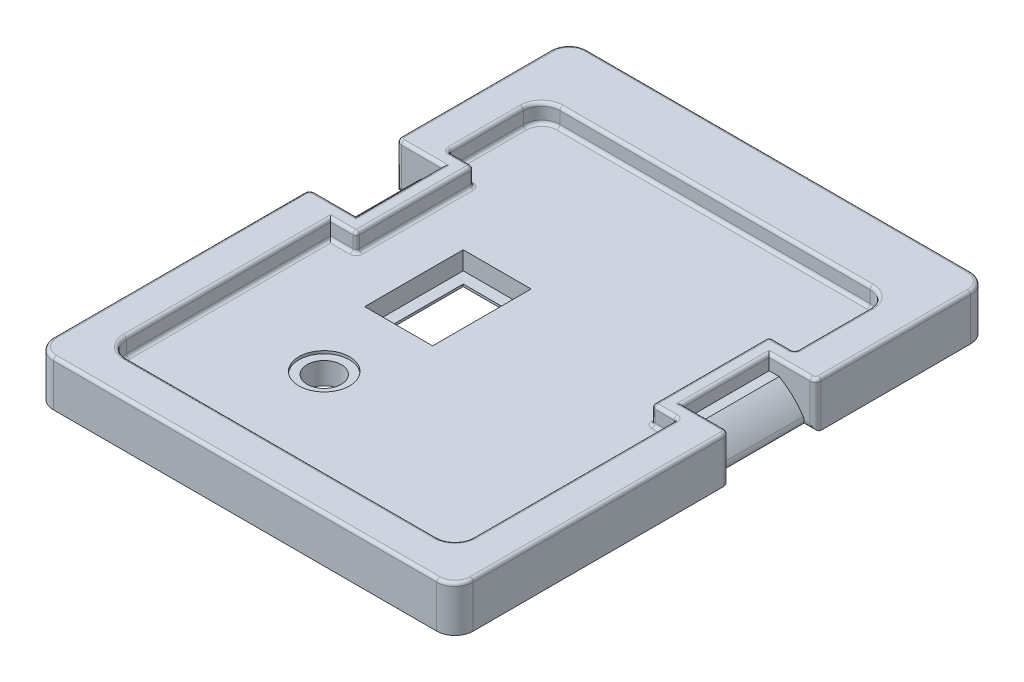
SolidWorks part; units mm, degrees
ref_plane "Front Plane" through (0, 0, 0) normal (0, 0, 1) x (1, 0, 0)
ref_plane "Top Plane" through (0, 0, 0) normal (0, 1, 0) x (1, 0, 0)
ref_plane "Right Plane" through (0, 0, 0) normal (1, 0, 0) x (0, 0, -1)
sketch "Sketch1" plane through (0, 0, 0) normal (0, 1, 0) x (1, 0, 0)
  line L1 (2, 0) -> (44, 0)
  line L2 (0, 2) -> (0, 56.5)
  line L3 (2, 58.5) -> (44, 58.5)
  line L4 (46, 2) -> (46, 56.5)
  arc A0 (0, 2) -> (2, 0) centre (2, 2) ccw
  arc A1 (44, 0) -> (46, 2) centre (44, 2) ccw
  arc A2 (46, 56.5) -> (44, 58.5) centre (44, 56.5) ccw
  arc A3 (2, 58.5) -> (0, 56.5) centre (2, 56.5) ccw
  point P7 (0, 0)
  point P10 (46, 0)
  point P13 (46, 58.5)
  dimension "D3" = 2
  dimension "D1" = 46
  dimension "D2" = 58.5
extrude "Boss-Extrude1" add sketch "Sketch1" along normal blind 5
sketch "Sketch2" plane through (0, 5, 0) normal (0, 1, 0) x (1, 0, 0)
  line L0 (4, 49.5) -> (4, 6)
  line L1 (0, 55.5) -> (46, 55.5)
  line L2 (0, 55.5) -> (0, 0)
  line L3 (0, 0) -> (46, 0)
  line L4 (46, 55.5) -> (46, 0)
  line L5 (6, 4) -> (40, 4)
  line L6 (42, 49.5) -> (42, 6)
  line L7 (6, 51.5) -> (40, 51.5)
  line L8 (42, 51.5) -> (42, 4) construction
  line L9 (4, 51.5) -> (42, 51.5) construction
  line L10 (4, 4) -> (42, 4) construction
  line L11 (4, 51.5) -> (4, 4) construction
  arc A0 (42, 49.5) -> (40, 51.5) centre (40, 49.5) ccw
  arc A1 (42, 6) -> (40, 4) centre (40, 6) cw
  arc A2 (6, 4) -> (4, 6) centre (6, 6) cw
  arc A3 (4, 49.5) -> (6, 51.5) centre (6, 49.5) cw
  dimension "D4" = 2
  dimension "D1" = 55.5
  dimension "D2" = 46
  dimension "D3" = 4
extrude "Cut-Extrude1" cut sketch "Sketch2" against normal blind 2 contours A3 L0 A2 L5 A1 L6 A0 L7
sketch "Sketch3" plane through (46, 0, 0) normal (1, 0, 0) x (0, 0, -1)
  line L0 (30.0677, 5) -> (30.0677, 3.3999)
  line L1 (2, 5) -> (56.5, 5) construction
  line L2 (30.0677, 3.3999) -> (39.5327, 3.3999)
  line L3 (39.5327, 3.3999) -> (39.5327, 5)
  line L4 (39.5327, 5) -> (30.0677, 5)
extrude "Cut-Extrude2" cut sketch "Sketch3" against normal up to surface (46 mm away) up to face at (0, 2.5, -29.25)
fillet "Fillet2" radius 8 2 edges at (46, 3.3999, -34.8002) (0, 3.3999, -34.8002)
fillet "Fillet3" radius 0.6 2 edges at (0.8201, 0, -34.8002) (45.1799, 0, -34.8002)
fillet "Fillet4" radius 0.6 8 edges at (46, 2.5, -39.5327) (45.0707, 0, -39.5327) (46, 2.5, -30.0677) (45.0707, 0, -30.0677) (0, 2.5, -39.5327) (0.9293, 0, -39.5327) (0.9293, 0, -30.0677) (0, 2.5, -30.0677)
sketch "Sketch4" plane through (0, 3, 0) normal (0, 1, 0) x (1, 0, 0)
  line L0 (4, 39.5327) -> (5.1, 39.5327)
  line L1 (5.1, 39.5327) -> (5.1, 30.0677)
  line L2 (5.1, 30.0677) -> (4, 30.0677)
  line L3 (4, 39.5327) -> (4, 41.2327)
  line L4 (4, 49.5) -> (4, 6) construction
  line L5 (4, 41.2327) -> (6.8, 41.2327)
  line L6 (6.8, 41.2327) -> (6.8, 28.3677)
  line L7 (6.8, 28.3677) -> (4, 28.3677)
  line L8 (4, 30.0677) -> (4, 6) construction
  line L9 (4, 30.0677) -> (4, 28.3677)
  line L10 (23, 51.5) -> (23, 4) construction
  line L11 (6, 51.5) -> (40, 51.5) construction
  line L12 (6, 4) -> (40, 4) construction
  line L13 (40.9, 30.0677) -> (42, 30.0677)
  line L14 (40.9, 39.5327) -> (40.9, 30.0677)
  line L15 (42, 39.5327) -> (40.9, 39.5327)
  line L16 (42, 39.5327) -> (42, 41.2327)
  line L17 (42, 41.2327) -> (39.2, 41.2327)
  line L18 (39.2, 41.2327) -> (39.2, 28.3677)
  line L19 (39.2, 28.3677) -> (42, 28.3677)
  line L20 (42, 30.0677) -> (42, 28.3677)
  dimension "D1" = 1.7
  dimension "D2" = 1.7
  dimension "D3" = 1.7
  dimension "D4" = 1.1
extrude "Boss-Extrude2" add sketch "Sketch4" along normal up to surface (2 mm away) up to face at (23, 5, -47.986)
fillet "Fillet5" radius 0.35 59 edges at (5.4, 3, -41.2327) (5.4, 3, -28.3677) (40.6, 3, -28.3677) (42, 3, -45.3663) (41.4142, 3, -50.9142) (23, 3, -51.5) (4.5858, 3, -50.9142) (4, 3, -17.1839) (4.5858, 3, -4.5858) (41.4142, 3, -4.5858) (4, 3, -45.3663) (4, 4, -41.2327) (6.8, 4, -41.2327) (6.8, 3, -34.8002) (6.8, 4, -28.3677) (23, 3, -4) (42, 3, -17.1839) (42, 4, -28.3677) (39.2, 4, -28.3677) (39.2, 3, -34.8002) (39.2, 4, -41.2327) (40.6, 3, -41.2327) (42, 4, -41.2327) (45.4142, 5, -0.5858) (23, 5, 0) (0.5858, 5, -0.5858) (0, 5, -15.7339) (0.1757, 5, -29.892) (2.85, 5, -30.0677) (5.1, 5, -34.8002) (2.85, 5, -39.5327) (0.1757, 5, -39.7084) (0, 5, -48.3163) (0.5858, 5, -57.9142) (23, 5, -58.5) (45.4142, 5, -57.9142) (46, 5, -48.3163) (45.8243, 5, -39.7084) (43.15, 5, -39.5327) (40.9, 5, -34.8002) (43.15, 5, -30.0677) (45.8243, 5, -29.892) (46, 5, -15.7339) (39.2, 5, -34.8002) (40.6, 5, -41.2327) (42, 5, -45.3663) (41.4142, 5, -50.9142) (23, 5, -51.5) (4.5858, 5, -50.9142) (4, 5, -45.3663) (5.4, 5, -41.2327) (6.8, 5, -34.8002) (5.4, 5, -28.3677) (4, 5, -17.1839) (4.5858, 5, -4.5858) (23, 5, -4) (41.4142, 5, -4.5858) (42, 5, -17.1839) (40.6, 5, -28.3677)
sketch "Sketch5" plane through (0, 3, 0) normal (0, 1, 0) x (1, 0, 0)
  line L1 (4, 39.5327) -> (5.1, 39.5327)
  line L2 (4, 39.5327) -> (4, 30.0677)
  line L3 (4, 30.0677) -> (5.1, 30.0677)
  line L4 (5.1, 39.5327) -> (5.1, 30.0677)
  line L5 (40.9, 39.5327) -> (42, 39.5327)
  line L6 (40.9, 39.5327) -> (40.9, 30.0677)
  line L7 (40.9, 30.0677) -> (42, 30.0677)
  line L8 (42, 39.5327) -> (42, 30.0677)
extrude "Boss-Extrude3" add sketch "Sketch5" along normal up to vertex (0.3999 mm away)
sketch "Sketch6" plane through (0, 5, 0) normal (0, 1, 0) x (1, 0, 0)
  line L0 (19.6946, 34.65) -> (19.6946, 23.85)
  line L1 (19.6946, 23.85) -> (12.25, 23.85)
  line L2 (12.25, 23.85) -> (12.25, 34.65)
  line L3 (12.25, 34.65) -> (19.6946, 34.65)
extrude "Cut-Extrude3" cut sketch "Sketch6" against normal up to surface (5 mm away) up to face at (23, 0, -32.0251)
sketch "Sketch7" plane through (0, 0, 0) normal (0, -1, 0) x (1, 0, 0)
  line L0 (13.5, -33.4) -> (13.5, -25.1)
  line L1 (12.25, -34.65) -> (19.6946, -34.65)
  line L2 (12.25, -34.65) -> (12.25, -23.85)
  line L3 (12.25, -23.85) -> (19.6946, -23.85)
  line L4 (19.6946, -34.65) -> (19.6946, -23.85)
  line L5 (13.5, -25.1) -> (18.4446, -25.1)
  line L6 (18.4446, -33.4) -> (18.4446, -25.1)
  line L7 (13.5, -33.4) -> (18.4446, -33.4)
  dimension "D1" = 1.25
extrude "Boss-Extrude4" add sketch "Sketch7" against normal blind 1
chamfer "Chamfer1" distance 0.75 angle 45 4 edges at (15.9723, 0, -25.1) (18.4446, 0, -29.25) (13.5, 0, -29.25) (15.9723, 0, -33.4)
sketch "Sketch8" plane through (0, 30, 0) normal (0, 1, 0) x (1, 0, 0)
  circle A0 centre (16.1689, 15.5) radius 1.875
extrude "Cut-Extrude4" cut sketch "Sketch8" against normal up to surface (30 mm away) up to face at (15.9723, 0, -29.25)
sketch "Sketch10" plane through (0, 3, 0) normal (0, 1, 0) x (1, 0, 0)
  circle A1 centre (16.1689, 15.5) radius 2.775
extrude "Cut-Extrude5" cut sketch "Sketch10" against normal blind 0.3
sketch "Sketch11" plane through (0, 0, 0) normal (0, -1, 0) x (1, 0, 0)
  circle A0 centre (16.1689, -15.5) radius 2.5
  dimension "D1" = 5
extrude "Cut-Extrude6" cut sketch "Sketch11" against normal blind 0.3
